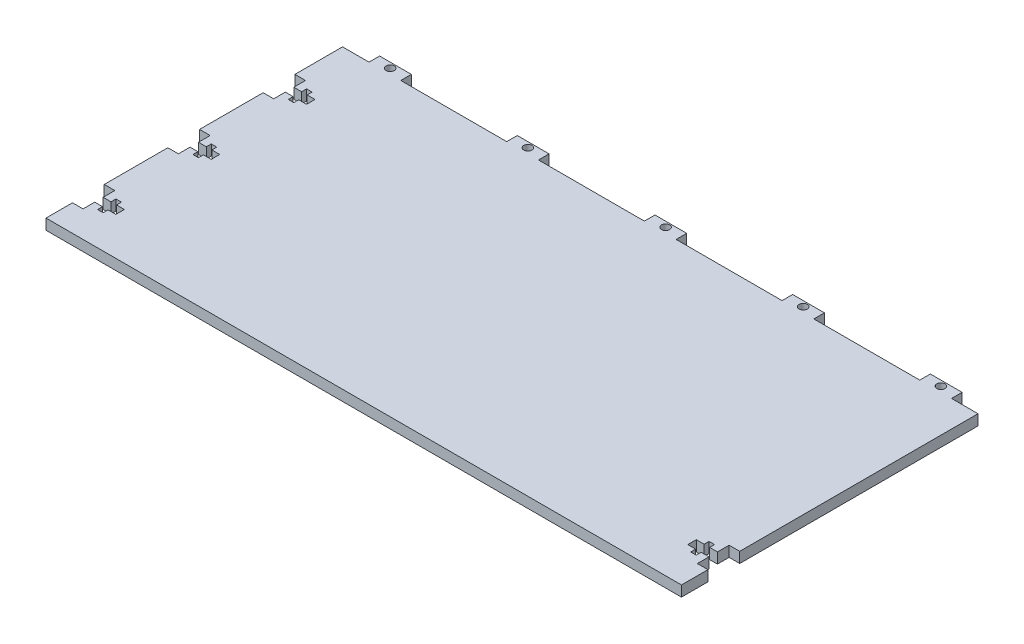
SolidWorks part; units mm, degrees
ref_plane "Front Plane" through (0, 0, 0) normal (0, 0, 1) x (1, 0, 0)
ref_plane "Top Plane" through (0, 0, 0) normal (0, 1, 0) x (1, 0, 0)
ref_plane "Right Plane" through (0, 0, 0) normal (1, 0, 0) x (0, 0, -1)
sketch "Sketch1" plane through (0, 0, 0) normal (0, 1, 0) x (1, 0, 0)
  line L1 (0, 0) -> (381, 0)
  line L2 (0, 0) -> (0, 177.8)
  line L3 (0, 177.8) -> (381, 177.8)
  line L4 (381, 0) -> (381, 177.8)
  dimension "D1" = 381
  dimension "D2" = 177.8
extrude "Boss-Extrude1" add sketch "Sketch1" along normal blind 6.35
sketch "Sketch2" plane through (0, 6.35, 0) normal (0, 1, 0) x (1, 0, 0)
  line L0 (381, 177.8) -> (0, 177.8) construction
  line L1 (15.875, 177.8) -> (34.925, 177.8)
  line L2 (15.875, 177.8) -> (15.875, 184.15)
  line L3 (15.875, 184.15) -> (34.925, 184.15)
  line L4 (34.925, 177.8) -> (34.925, 184.15)
  line L5 (0, 177.8) -> (0, 0) construction
  dimension "D1" = 19.05
  dimension "D2" = 6.35
  dimension "D3" = 15.875
extrude "Boss-Extrude2" add sketch "Sketch2" against normal blind 6.35
hole_wizard "#10 (0.1935) Diameter Hole1" positions "Sketch5" profile "Sketch4" hole size "#10" standard "ANSI Inch" end condition through all
sketch "Sketch5" plane through (0, 6.35, 0) normal (0, 1, 0) x (1, 0, 0)
  line L2 (15.875, 180.975) -> (34.925, 180.975) construction
  line L3 (15.875, 184.15) -> (15.875, 177.8) construction
  line L4 (34.925, 177.8) -> (34.925, 184.15) construction
  point P0 (25.4, 180.975)
sketch "Sketch4" plane through (25.4, 6.35, -180.975) normal (1, 0, 0) x (0, 0, 1)
  line L0 (0, 0) -> (0, 6.35)
  line L1 (0, 6.35) -> (2.4574, 6.35)
  line L2 (2.4574, 6.35) -> (2.4574, 0)
  line L5 (2.4574, 0) -> (0, 0)
  line L11 (0, -6.35) -> (0, 107.95) construction
  dimension "Thru Hole Dia." = 4.9149
  dimension "Thru Hole Depth" = 6.35
pattern_linear "LPattern1" count 5 spacing 82.55 along (1, 0, 0) of "#10 (0.1935) Diameter Hole1", "Boss-Extrude2"
sketch "Sketch7" plane through (0, 6.35, 0) normal (0, 1, 0) x (1, 0, 0)
  line L0 (0, 34.925) -> (0, 15.875)
  line L1 (0, 34.925) -> (6.35, 34.925)
  line L2 (6.35, 34.925) -> (6.35, 27.94)
  line L3 (0, 15.875) -> (6.35, 15.875)
  line L4 (6.35, 27.94) -> (11.049, 27.94)
  line L5 (19.05, 27.94) -> (19.05, 22.86)
  line L6 (6.35, 22.86) -> (11.049, 22.86)
  line L7 (14.351, 27.94) -> (19.05, 27.94)
  line L8 (14.351, 30.8991) -> (14.351, 27.94)
  line L9 (14.351, 30.8991) -> (11.049, 30.8991)
  line L10 (11.049, 30.8991) -> (11.049, 27.94)
  line L11 (14.351, 19.9009) -> (11.049, 19.9009)
  line L12 (14.351, 22.86) -> (14.351, 19.9009)
  line L13 (14.351, 22.86) -> (19.05, 22.86)
  line L14 (11.049, 22.86) -> (11.049, 19.9009)
  line L15 (6.35, 22.86) -> (6.35, 15.875)
  line L16 (0, 177.8) -> (0, 0) construction
  line L17 (15.875, 177.8) -> (0, 177.8) construction
  point P8 (19.05, 25.4)
  dimension "D1" = 6.35
  dimension "D2" = 5.08
  dimension "D3" = 12.7
  dimension "D4" = 10.9982
  dimension "D5" = 3.302
  dimension "D6" = 19.05
  dimension "D7" = 142.875
extrude "Cut-Extrude2" cut sketch "Sketch7" against normal through all
ref_plane "Plane2" through (190.5, 0, 0) normal (-1, 0, 0) x (0, 0, 1)
mirror "Mirror2" about plane through (190.5, 0, 0) normal (-1, 0, 0) of "Cut-Extrude2"
pattern_linear "LPattern4" count 3 spacing 57.15 along (0, 0, -1) of "Cut-Extrude2"
